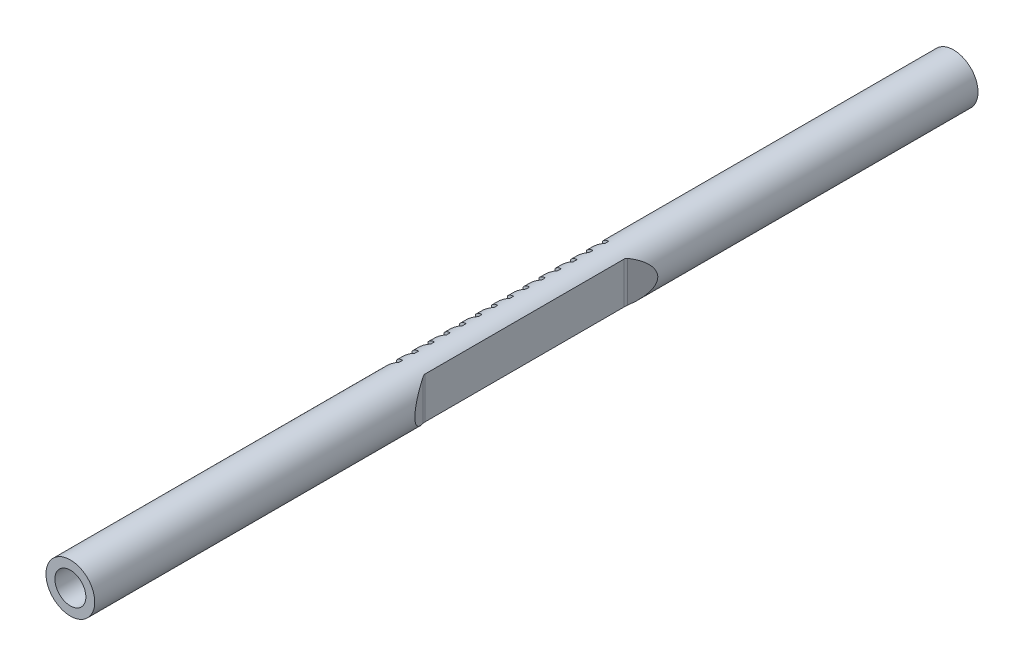
SolidWorks part; units mm, degrees
material "6061-T6 (SS)"
ref_plane "Front Plane" through (0, 0, 0) normal (0, 0, 1) x (1, 0, 0)
ref_plane "Top Plane" through (0, 0, 0) normal (0, 1, 0) x (1, 0, 0)
ref_plane "Right Plane" through (0, 0, 0) normal (1, 0, 0) x (0, 0, -1)
sketch "Sketch1" plane through (0, 0, 0) normal (0, 0, 1) x (1, 0, 0)
  circle A0 centre (0, 0) radius 10.3025
  dimension "D1" = 20.605
extrude "Boss-Extrude1" add sketch "Sketch1" along normal blind 390
sketch "Sketch2" plane through (0, 0, 0) normal (0, 0, -1) x (-1, 0, 0)
  circle A0 centre (0, 0) radius 6.5485
  dimension "D1" = 13.097
extrude "Cut-Extrude1" cut sketch "Sketch2" against normal blind 141.75
sketch "Sketch3" plane through (0, 0, 390) normal (0, 0, 1) x (1, 0, 0)
  circle A0 centre (0, 0) radius 6.5485
  dimension "D1" = 13.097
extrude "Cut-Extrude2" cut sketch "Sketch3" against normal blind 141.75
sketch "Sketch4" plane through (0, 0, 0) normal (0, 1, 0) x (1, 0, 0)
  line L29 (-7.6275, -243.825) -> (-7.6275, -146.225)
  line L32 (10.4382, -246.605) -> (10.4382, -143.4152)
  line L39 (-10.4275, -139.475) -> (-10.4275, -146.225) construction
  line L43 (6.1894, -195.0101) -> (10.4382, -195.0101) construction
  line L47 (-10.4275, -250.525) -> (-10.4275, -243.825) construction
  line L48 (-10.4275, -146.225) -> (-7.6275, -146.225)
  line L49 (-10.4275, -146.225) -> (-10.4275, -243.825)
  line L50 (-10.4275, -243.825) -> (-7.6275, -243.825)
  line L54 (10.4382, -246.605) -> (5.3963, -237.7115)
  line L55 (5.3963, -237.7115) -> (5.3963, -152.3086)
  line L56 (10.4382, -143.4152) -> (5.3963, -152.3086)
  point P10 (5.3963, -195.0101)
  point P15 (-7.6275, -195.025)
extrude "Cut-Extrude3" cut sketch "Sketch4" against normal blind 20 and the other way blind 20
sketch "Sketch5" plane through (0, 0, 0) normal (0, 1, 0) x (1, 0, 0)
  line L0 (-3.4275, -149.175) -> (-7.6275, -149.175) construction
  line L4 (-3.4275, -152.275) -> (-3.4275, -150.675)
  line L10 (-7.6275, -243.825) -> (-7.6275, -146.225) construction
  line L11 (-7.6275, -149.175) -> (-3.4275, -150.675)
  line L12 (-7.6275, -153.775) -> (-7.6275, -149.175)
  line L20 (-3.4275, -149.175) -> (-3.4275, -153.775) construction
  line L21 (-3.4275, -153.775) -> (-7.6275, -153.775) construction
  line L22 (-3.4275, -152.275) -> (-7.6275, -153.775)
extrude "Cut-Extrude4" cut sketch "Sketch5" against normal blind 20 and the other way blind 20
pattern_linear "LPattern1" count 14 spacing 6.7 along (0, 0, 1) of "Cut-Extrude4"
sketch "Sketch6" plane through (0, 0, 390) normal (0, 0, 1) x (1, 0, 0)
  line L1 (-12.3882, -12.5582) -> (12.3882, -12.5582)
  line L2 (-12.3882, -12.5582) -> (-12.3882, 12.5582)
  line L3 (-12.3882, 12.5582) -> (12.3882, 12.5582)
  line L4 (12.3882, -12.5582) -> (12.3882, 12.5582)
  line L5 (-12.3882, -12.5582) -> (12.3882, 12.5582) construction
  line L6 (-12.3882, 12.5582) -> (12.3882, -12.5582) construction
  point P0 (0, 0)
extrude "Cut-Extrude5" cut sketch "Sketch6" against normal blind 8.25
sketch "Sketch7" plane through (0, 0, 0) normal (0, 0, -1) x (-1, 0, 0)
  line L1 (-16.4527, -16.1861) -> (16.4527, -16.1861)
  line L2 (-16.4527, -16.1861) -> (-16.4527, 16.1861)
  line L3 (-16.4527, 16.1861) -> (16.4527, 16.1861)
  line L4 (16.4527, -16.1861) -> (16.4527, 16.1861)
  line L5 (-16.4527, -16.1861) -> (16.4527, 16.1861) construction
  line L6 (-16.4527, 16.1861) -> (16.4527, -16.1861) construction
  point P0 (0, 0)
extrude "Cut-Extrude6" cut sketch "Sketch7" against normal blind 8.25
fillet "Fillet2" radius 2.38 2 edges at (5.3963, 0, 237.7115) (5.3963, 0, 152.3086)
ref_plane "Plane1" through (0, 0, 58.25) normal (0, 0, -1) x (-1, 0, 0)
ref_plane "Plane2" through (0, 0, 351.75) normal (0, 0, 1) x (1, 0, 0)
